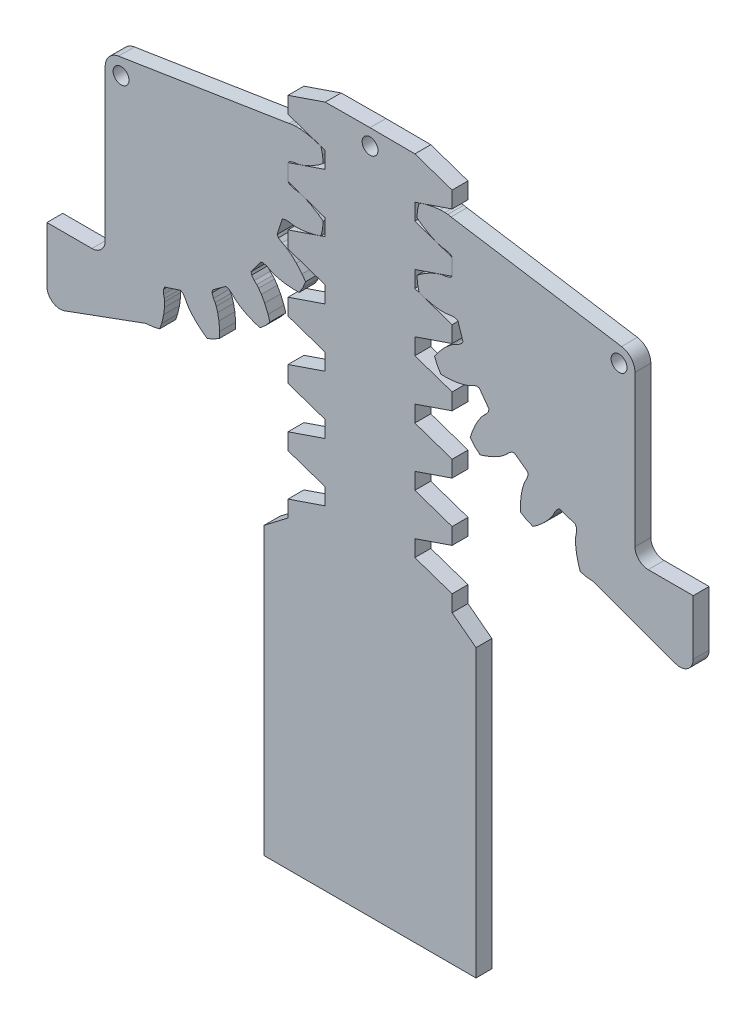
SolidWorks part; units mm, degrees
note: The reader was unsure of these and kept them because the rebuilt part matched: shared geometry of "Model<4>", "Model<5>".
other "verr_centre"
other "verr_droit"
other "verr_gauche"
ref_plane "Plan de face" through (0, 0, 0) normal (0, 0, 1) x (1, 0, 0)
ref_plane "Plan de dessus" through (0, 0, 0) normal (0, 1, 0) x (1, 0, 0)
ref_plane "Plan de droite" through (0, 0, 0) normal (1, 0, 0) x (0, 0, -1)
sketch "Model" plane through (0, 0, 0) normal (0, 0, 1) x (1, 0, 0)
  line L0 (-24, 288) -> (-24, 209.8426) construction
  line L1 (22.0859, 288) -> (22.0859, 218.9084) construction
  line L2 (0, 318) -> (0, 60) construction
  line L288 (24.6849, 293.2827) -> (26.4138, 292.6914)
  line L289 (26.4138, 292.6914) -> (27.4861, 292.4462)
  line L290 (27.4861, 292.4462) -> (28.7039, 292.2992)
  line L291 (28.7039, 292.2992) -> (30.2775, 291.8078)
  line L292 (30.2775, 291.8078) -> (31.0246, 291.1144)
  line L293 (31.0246, 291.1144) -> (31.0246, 284.8856)
  line L294 (31.0246, 284.8856) -> (30.2775, 284.1922)
  line L295 (30.2775, 284.1922) -> (28.7039, 283.7008)
  line L296 (28.7039, 283.7008) -> (27.4861, 283.5538)
  line L297 (27.4861, 283.5538) -> (26.4138, 283.3086)
  line L298 (26.4138, 283.3086) -> (24.6849, 282.7173)
  line L299 (24.6849, 282.7173) -> (22.3675, 281.6425)
  line L300 (22.3675, 281.6425) -> (19.5509, 279.958)
  line L301 (19.5509, 279.958) -> (17.7106, 278.5772)
  line L302 (17.7106, 278.5772) -> (17.9174, 275.9497)
  line L303 (17.9174, 275.9497) -> (18.5327, 273.3869)
  line L304 (18.5327, 273.3869) -> (20.7096, 272.6424)
  line L305 (20.7096, 272.6424) -> (23.9088, 271.9107)
  line L306 (23.9088, 271.9107) -> (26.445, 271.6046)
  line L307 (26.445, 271.6046) -> (28.272, 271.5765)
  line L308 (28.272, 271.5765) -> (29.3676, 271.6746)
  line L309 (29.3676, 271.6746) -> (30.5712, 271.9112)
  line L310 (30.5712, 271.9112) -> (32.2197, 271.9301)
  line L311 (32.2197, 271.9301) -> (33.1445, 271.5015)
  line L312 (33.1445, 271.5015) -> (35.0693, 265.5776)
  line L313 (35.0693, 265.5776) -> (34.573, 264.6873)
  line L314 (34.573, 264.6873) -> (33.2283, 263.7336)
  line L315 (33.2283, 263.7336) -> (32.1155, 263.2175)
  line L316 (32.1155, 263.2175) -> (31.1714, 262.6529)
  line L317 (31.1714, 262.6529) -> (29.7099, 261.5563)
  line L318 (29.7099, 261.5563) -> (27.838, 259.818)
  line L319 (27.838, 259.818) -> (25.6798, 257.3456)
  line L320 (25.6798, 257.3456) -> (24.3563, 255.4636)
  line L321 (24.3563, 255.4636) -> (25.3649, 253.0287)
  line L322 (25.3649, 253.0287) -> (26.742, 250.7814)
  line L323 (26.742, 250.7814) -> (29.0425, 250.746)
  line L324 (29.0425, 250.746) -> (32.3112, 251.0388)
  line L325 (32.3112, 251.0388) -> (34.8178, 251.5314)
  line L326 (34.8178, 251.5314) -> (36.5641, 252.0693)
  line L327 (36.5641, 252.0693) -> (37.5757, 252.5011)
  line L328 (37.5757, 252.5011) -> (38.6474, 253.098)
  line L329 (38.6474, 253.098) -> (40.2093, 253.6254)
  line L330 (40.2093, 253.6254) -> (41.2213, 253.5036)
  line L331 (41.2213, 253.5036) -> (44.8825, 248.4644)
  line L332 (44.8825, 248.4644) -> (44.6856, 247.4643)
  line L333 (44.6856, 247.4643) -> (43.7014, 246.1418)
  line L334 (43.7014, 246.1418) -> (42.8025, 245.3071)
  line L335 (42.8025, 245.3071) -> (42.0792, 244.4784)
  line L336 (42.0792, 244.4784) -> (41.028, 242.9838)
  line L337 (41.028, 242.9838) -> (39.7849, 240.7521)
  line L338 (39.7849, 240.7521) -> (38.4964, 237.7338)
  line L339 (38.4964, 237.7338) -> (37.8192, 235.535)
  line L340 (37.8192, 235.535) -> (39.5309, 233.5309)
  line L341 (39.5309, 233.5309) -> (41.535, 231.8192)
  line L342 (41.535, 231.8192) -> (43.7338, 232.4964)
  line L343 (43.7338, 232.4964) -> (46.7521, 233.7849)
  line L344 (46.7521, 233.7849) -> (48.9838, 235.028)
  line L345 (48.9838, 235.028) -> (50.4784, 236.0792)
  line L346 (50.4784, 236.0792) -> (51.3071, 236.8025)
  line L347 (51.3071, 236.8025) -> (52.1418, 237.7014)
  line L348 (52.1418, 237.7014) -> (53.4643, 238.6856)
  line L349 (53.4643, 238.6856) -> (54.4644, 238.8825)
  line L350 (54.4644, 238.8825) -> (59.5036, 235.2213)
  line L351 (59.5036, 235.2213) -> (59.6254, 234.2093)
  line L352 (59.6254, 234.2093) -> (59.098, 232.6474)
  line L353 (59.098, 232.6474) -> (58.5011, 231.5757)
  line L354 (58.5011, 231.5757) -> (58.0693, 230.5641)
  line L355 (58.0693, 230.5641) -> (57.5314, 228.8178)
  line L356 (57.5314, 228.8178) -> (57.0388, 226.3112)
  line L357 (57.0388, 226.3112) -> (56.746, 223.0425)
  line L358 (56.746, 223.0425) -> (56.7814, 220.742)
  line L359 (56.7814, 220.742) -> (59.0287, 219.3649)
  line L360 (59.0287, 219.3649) -> (61.4636, 218.3563)
  line L361 (61.4636, 218.3563) -> (63.3456, 219.6798)
  line L362 (63.3456, 219.6798) -> (65.818, 221.838)
  line L363 (65.818, 221.838) -> (67.5563, 223.7099)
  line L364 (67.5563, 223.7099) -> (68.6529, 225.1714)
  line L365 (68.6529, 225.1714) -> (69.2175, 226.1155)
  line L366 (69.2175, 226.1155) -> (69.7336, 227.2283)
  line L367 (69.7336, 227.2283) -> (70.6873, 228.573)
  line L368 (70.6873, 228.573) -> (71.5776, 229.0693)
  line L369 (71.5776, 229.0693) -> (77.5015, 227.1445)
  line L370 (77.5015, 227.1445) -> (77.9301, 226.2197)
  line L371 (77.9301, 226.2197) -> (77.9112, 224.5712)
  line L372 (77.9112, 224.5712) -> (77.6746, 223.3676)
  line L373 (77.6746, 223.3676) -> (77.5765, 222.272)
  line L374 (77.5765, 222.272) -> (77.6046, 220.445)
  line L375 (77.6046, 220.445) -> (77.9107, 217.9088)
  line L376 (77.9107, 217.9088) -> (78.6424, 214.7096)
  line L377 (78.6424, 214.7096) -> (79.3869, 212.5327)
  line L378 (79.3869, 212.5327) -> (81.9497, 211.9174)
  line L379 (81.9497, 211.9174) -> (84.5772, 211.7106)
  line L380 (84.5772, 211.7106) -> (115.2804, 200.4655)
  line L381 (122, 205.1605) -> (122, 226)
  line L382 (122, 226) -> (105, 226)
  line L383 (100, 231) -> (100, 288)
  line L384 (94.9357, 293.9266) -> (30.5712, 304.0888)
  line L385 (30.5712, 304.0888) -> (29.3676, 304.3254)
  line L386 (29.3676, 304.3254) -> (28.272, 304.4235)
  line L387 (28.272, 304.4235) -> (26.445, 304.3954)
  line L388 (26.445, 304.3954) -> (23.9088, 304.0893)
  line L389 (23.9088, 304.0893) -> (20.7096, 303.3576)
  line L390 (20.7096, 303.3576) -> (18.5327, 302.6131)
  line L391 (18.5327, 302.6131) -> (17.9174, 300.0503)
  line L392 (17.9174, 300.0503) -> (17.7106, 297.4228)
  line L393 (17.7106, 297.4228) -> (19.5509, 296.042)
  line L394 (19.5509, 296.042) -> (22.3675, 294.3575)
  line L395 (22.3675, 294.3575) -> (24.6849, 293.2827)
  line L396 (-24.6849, 293.2827) -> (-26.4138, 292.6914)
  line L397 (-26.4138, 292.6914) -> (-27.4861, 292.4462)
  line L398 (-27.4861, 292.4462) -> (-28.7039, 292.2992)
  line L399 (-28.7039, 292.2992) -> (-30.2775, 291.8078)
  line L400 (-30.2775, 291.8078) -> (-31.0246, 291.1144)
  line L401 (-31.0246, 291.1144) -> (-31.0246, 284.8856)
  line L402 (-31.0246, 284.8856) -> (-30.2775, 284.1922)
  line L403 (-30.2775, 284.1922) -> (-28.7039, 283.7008)
  line L404 (-28.7039, 283.7008) -> (-27.4861, 283.5538)
  line L405 (-27.4861, 283.5538) -> (-26.4138, 283.3086)
  line L406 (-26.4138, 283.3086) -> (-24.6849, 282.7173)
  line L407 (-24.6849, 282.7173) -> (-22.3675, 281.6425)
  line L408 (-22.3675, 281.6425) -> (-19.5509, 279.958)
  line L409 (-19.5509, 279.958) -> (-17.7106, 278.5772)
  line L410 (-17.7106, 278.5772) -> (-17.9174, 275.9497)
  line L411 (-17.9174, 275.9497) -> (-18.5327, 273.3869)
  line L412 (-18.5327, 273.3869) -> (-20.7096, 272.6424)
  line L413 (-20.7096, 272.6424) -> (-23.9088, 271.9107)
  line L414 (-23.9088, 271.9107) -> (-26.445, 271.6046)
  line L415 (-26.445, 271.6046) -> (-28.272, 271.5765)
  line L416 (-28.272, 271.5765) -> (-29.3676, 271.6746)
  line L417 (-29.3676, 271.6746) -> (-30.5712, 271.9112)
  line L418 (-30.5712, 271.9112) -> (-32.2197, 271.9301)
  line L419 (-32.2197, 271.9301) -> (-33.1445, 271.5015)
  line L420 (-33.1445, 271.5015) -> (-35.0693, 265.5776)
  line L421 (-35.0693, 265.5776) -> (-34.573, 264.6873)
  line L422 (-34.573, 264.6873) -> (-33.2283, 263.7336)
  line L423 (-33.2283, 263.7336) -> (-32.1155, 263.2175)
  line L424 (-32.1155, 263.2175) -> (-31.1714, 262.6529)
  line L425 (-31.1714, 262.6529) -> (-29.7099, 261.5563)
  line L426 (-29.7099, 261.5563) -> (-27.838, 259.818)
  line L427 (-27.838, 259.818) -> (-25.6798, 257.3456)
  line L428 (-25.6798, 257.3456) -> (-24.3563, 255.4636)
  line L429 (-24.3563, 255.4636) -> (-25.3649, 253.0287)
  line L430 (-25.3649, 253.0287) -> (-26.742, 250.7814)
  line L431 (-26.742, 250.7814) -> (-29.0425, 250.746)
  line L432 (-29.0425, 250.746) -> (-32.3112, 251.0388)
  line L433 (-32.3112, 251.0388) -> (-34.8178, 251.5314)
  line L434 (-34.8178, 251.5314) -> (-36.5641, 252.0693)
  line L435 (-36.5641, 252.0693) -> (-37.5757, 252.5011)
  line L436 (-37.5757, 252.5011) -> (-38.6474, 253.098)
  line L437 (-38.6474, 253.098) -> (-40.2093, 253.6254)
  line L438 (-40.2093, 253.6254) -> (-41.2213, 253.5036)
  line L439 (-41.2213, 253.5036) -> (-44.8825, 248.4644)
  line L440 (-44.8825, 248.4644) -> (-44.6856, 247.4643)
  line L441 (-44.6856, 247.4643) -> (-43.7014, 246.1418)
  line L442 (-43.7014, 246.1418) -> (-42.8025, 245.3071)
  line L443 (-42.8025, 245.3071) -> (-42.0792, 244.4784)
  line L444 (-42.0792, 244.4784) -> (-41.028, 242.9838)
  line L445 (-41.028, 242.9838) -> (-39.7849, 240.7521)
  line L446 (-39.7849, 240.7521) -> (-38.4964, 237.7338)
  line L447 (-38.4964, 237.7338) -> (-37.8192, 235.535)
  line L448 (-37.8192, 235.535) -> (-39.5309, 233.5309)
  line L449 (-39.5309, 233.5309) -> (-41.535, 231.8192)
  line L450 (-41.535, 231.8192) -> (-43.7338, 232.4964)
  line L451 (-43.7338, 232.4964) -> (-46.7521, 233.7849)
  line L452 (-46.7521, 233.7849) -> (-48.9838, 235.028)
  line L453 (-48.9838, 235.028) -> (-50.4784, 236.0792)
  line L454 (-50.4784, 236.0792) -> (-51.3071, 236.8025)
  line L455 (-51.3071, 236.8025) -> (-52.1418, 237.7014)
  line L456 (-52.1418, 237.7014) -> (-53.4643, 238.6856)
  line L457 (-53.4643, 238.6856) -> (-54.4644, 238.8825)
  line L458 (-54.4644, 238.8825) -> (-59.5036, 235.2213)
  line L459 (-59.5036, 235.2213) -> (-59.6254, 234.2093)
  line L460 (-59.6254, 234.2093) -> (-59.098, 232.6474)
  line L461 (-59.098, 232.6474) -> (-58.5011, 231.5757)
  line L462 (-58.5011, 231.5757) -> (-58.0693, 230.5641)
  line L463 (-58.0693, 230.5641) -> (-57.5314, 228.8178)
  line L464 (-57.5314, 228.8178) -> (-57.0388, 226.3112)
  line L465 (-57.0388, 226.3112) -> (-56.746, 223.0425)
  line L466 (-56.746, 223.0425) -> (-56.7814, 220.742)
  line L467 (-56.7814, 220.742) -> (-59.0287, 219.3649)
  line L468 (-59.0287, 219.3649) -> (-61.4636, 218.3563)
  line L469 (-61.4636, 218.3563) -> (-63.3456, 219.6798)
  line L470 (-63.3456, 219.6798) -> (-65.818, 221.838)
  line L471 (-65.818, 221.838) -> (-67.5563, 223.7099)
  line L472 (-67.5563, 223.7099) -> (-68.6529, 225.1714)
  line L473 (-68.6529, 225.1714) -> (-69.2175, 226.1155)
  line L474 (-69.2175, 226.1155) -> (-69.7336, 227.2283)
  line L475 (-69.7336, 227.2283) -> (-70.6873, 228.573)
  line L476 (-70.6873, 228.573) -> (-71.5776, 229.0693)
  line L477 (-71.5776, 229.0693) -> (-77.5015, 227.1445)
  line L478 (-77.5015, 227.1445) -> (-77.9301, 226.2197)
  line L479 (-77.9301, 226.2197) -> (-77.9112, 224.5712)
  line L480 (-77.9112, 224.5712) -> (-77.6746, 223.3676)
  line L481 (-77.6746, 223.3676) -> (-77.5765, 222.272)
  line L482 (-77.5765, 222.272) -> (-77.6046, 220.445)
  line L483 (-77.6046, 220.445) -> (-77.9107, 217.9088)
  line L484 (-77.9107, 217.9088) -> (-78.6424, 214.7096)
  line L485 (-78.6424, 214.7096) -> (-79.3869, 212.5327)
  line L486 (-79.3869, 212.5327) -> (-81.9497, 211.9174)
  line L487 (-81.9497, 211.9174) -> (-84.5772, 211.7106)
  line L488 (-84.5772, 211.7106) -> (-115.2804, 200.4655)
  line L489 (-122, 205.1605) -> (-122, 226)
  line L490 (-122, 226) -> (-105, 226)
  line L491 (-100, 231) -> (-100, 288)
  line L492 (-94.9357, 293.9266) -> (-30.5712, 304.0888)
  line L493 (-30.5712, 304.0888) -> (-29.3676, 304.3254)
  line L494 (-29.3676, 304.3254) -> (-28.272, 304.4235)
  line L495 (-28.272, 304.4235) -> (-26.445, 304.3954)
  line L496 (-26.445, 304.3954) -> (-23.9088, 304.0893)
  line L497 (-23.9088, 304.0893) -> (-20.7096, 303.3576)
  line L498 (-20.7096, 303.3576) -> (-18.5327, 302.6131)
  line L499 (-18.5327, 302.6131) -> (-17.9174, 300.0503)
  line L500 (-17.9174, 300.0503) -> (-17.7106, 297.4228)
  line L501 (-17.7106, 297.4228) -> (-19.5509, 296.042)
  line L502 (-19.5509, 296.042) -> (-22.3675, 294.3575)
  line L503 (-22.3675, 294.3575) -> (-24.6849, 293.2827)
  line L504 (-40, 60) -> (0, 60)
  line L505 (0, 60) -> (40, 60)
  line L506 (40, 60) -> (40, 168)
  line L507 (40, 168) -> (30.9746, 174.9084)
  line L508 (30.9746, 174.9084) -> (30.9746, 181.0916)
  line L509 (30.9746, 181.0916) -> (16.919, 185.8989)
  line L510 (16.919, 185.8989) -> (16.919, 192.1011)
  line L511 (16.919, 192.1011) -> (30.9746, 196.9084)
  line L512 (30.9746, 196.9084) -> (30.9746, 203.0916)
  line L513 (30.9746, 203.0916) -> (16.919, 207.8989)
  line L514 (16.919, 207.8989) -> (16.919, 214.1011)
  line L515 (16.919, 214.1011) -> (30.9746, 218.9084)
  line L516 (30.9746, 218.9084) -> (30.9746, 225.0916)
  line L517 (30.9746, 225.0916) -> (16.919, 229.8989)
  line L518 (16.919, 229.8989) -> (16.919, 236.1011)
  line L519 (16.919, 236.1011) -> (30.9746, 240.9084)
  line L520 (30.9746, 240.9084) -> (30.9746, 247.0916)
  line L521 (30.9746, 247.0916) -> (16.919, 251.8989)
  line L522 (16.919, 251.8989) -> (16.919, 258.1011)
  line L523 (16.919, 258.1011) -> (30.9746, 262.9084)
  line L524 (30.9746, 262.9084) -> (30.9746, 269.0916)
  line L525 (30.9746, 269.0916) -> (16.919, 273.8989)
  line L526 (16.919, 273.8989) -> (16.919, 280.1011)
  line L527 (16.919, 280.1011) -> (30.9746, 284.9084)
  line L528 (30.9746, 284.9084) -> (30.9746, 291.0916)
  line L529 (30.9746, 291.0916) -> (16.919, 295.8989)
  line L530 (16.919, 295.8989) -> (16.919, 302.1011)
  line L531 (16.919, 302.1011) -> (30.9746, 306.9084)
  line L532 (30.9746, 306.9084) -> (30.9746, 313.0916)
  line L533 (30.9746, 313.0916) -> (16.919, 317.8989)
  line L534 (16.919, 317.8989) -> (0, 318)
  line L535 (0, 318) -> (-16.919, 317.8989)
  line L536 (-16.919, 317.8989) -> (-30.9746, 313.0916)
  line L537 (-30.9746, 313.0916) -> (-30.9746, 306.9084)
  line L538 (-30.9746, 306.9084) -> (-16.919, 302.1011)
  line L539 (-16.919, 302.1011) -> (-16.919, 295.8989)
  line L540 (-16.919, 295.8989) -> (-30.9746, 291.0916)
  line L541 (-30.9746, 291.0916) -> (-30.9746, 284.9084)
  line L542 (-30.9746, 284.9084) -> (-16.919, 280.1011)
  line L543 (-16.919, 280.1011) -> (-16.919, 273.8989)
  line L544 (-16.919, 273.8989) -> (-30.9746, 269.0916)
  line L545 (-30.9746, 269.0916) -> (-30.9746, 262.9084)
  line L546 (-30.9746, 262.9084) -> (-16.919, 258.1011)
  line L547 (-16.919, 258.1011) -> (-16.919, 251.8989)
  line L548 (-16.919, 251.8989) -> (-30.9746, 247.0916)
  line L549 (-30.9746, 247.0916) -> (-30.9746, 240.9084)
  line L550 (-30.9746, 240.9084) -> (-16.919, 236.1011)
  line L551 (-16.919, 236.1011) -> (-16.919, 229.8989)
  line L552 (-16.919, 229.8989) -> (-30.9746, 225.0916)
  line L553 (-30.9746, 225.0916) -> (-30.9746, 218.9084)
  line L554 (-30.9746, 218.9084) -> (-16.919, 214.1011)
  line L555 (-16.919, 214.1011) -> (-16.919, 207.8989)
  line L556 (-16.919, 207.8989) -> (-30.9746, 203.0916)
  line L557 (-30.9746, 203.0916) -> (-30.9746, 196.9084)
  line L558 (-30.9746, 196.9084) -> (-16.919, 192.1011)
  line L559 (-16.919, 192.1011) -> (-16.919, 185.8989)
  line L560 (-16.919, 185.8989) -> (-30.9746, 181.0916)
  line L561 (-30.9746, 181.0916) -> (-30.9746, 174.9084)
  line L562 (-30.9746, 174.9084) -> (-40, 168)
  line L563 (-40, 168) -> (-40, 60)
  circle A0 centre (94, 288) radius 3
  circle A1 centre (0, 312) radius 3
  circle A5 centre (-94, 288) radius 70 construction
  circle A6 centre (94, 288) radius 71.9141 construction
  arc A8 (115.2804, 200.4655) -> (122, 205.1605) centre (117, 205.1605) ccw
  arc A9 (100, 231) -> (105, 226) centre (105, 231) ccw
  arc A10 (100, 288) -> (94.9357, 293.9266) centre (94, 288) ccw
  arc A11 (-122, 205.1605) -> (-115.2804, 200.4655) centre (-117, 205.1605) ccw
  arc A12 (-105, 226) -> (-100, 231) centre (-105, 231) ccw
  arc A13 (-94.9357, 293.9266) -> (-100, 288) centre (-94, 288) ccw
  circle A14 centre (-94, 288) radius 3
extrude "Boss.-Extru.1" add sketch "Model" along normal blind 6 contours A1 | L536 L537 L538 L539 L540 L541 L542 L543 L544 L545 L546 L547 L548 L549 L550 L551 L552 L553 L554 L555 L556 L557 L558 L559 L560 L561 L562 L563 L504 L505 L506 L507 L508 L509 L510 L511 L512 L513 L514 L515 L516 L517 L518 L519 L520 L521 L522 L523 L524 L525 L526 L527 L528 L529 L530 L531 L532 L533 L534 L535
extrude "Boss.-Extru.2" add sketch "Model<4>" along normal blind 6 separate body contours L492 A13 L491 A12 L490 L489 A11 L488 L487 L486 L485 L484 L483 L482 L481 L480 L479 L478 L477 L476 L475 L474 L473 L472 L471 L470 L469 L468 L467 L466 L465 L464 L463 L462 L461 L460 L459 L458 L457 L456 L455 L454 L453 L452 L451 L450 L449 L448 L447 L446 L445
sketch "Model<4>" plane through (0, 0, 0) normal (0, 0, 1) x (1, 0, 0) same geometry as "Model"
extrude "Boss.-Extru.3" add sketch "Model<5>" along normal blind 6 separate body contours L383 A10 L384 L385 L386 L387 L388 L389 L390 L391 L392 L393 L394 L395 L288 L289 L290 L291 L292 L293 L294 L295 L296 L297 L298 L299 L300 L301 L302 L303 L304 L305 L306 L307 L308 L309 L310 L311 L312 L313 L314 L315 L316 L317 L318 L319 L320 L321 L322 L323 L324
sketch "Model<5>" plane through (0, 0, 0) normal (0, 0, 1) x (1, 0, 0) same geometry as "Model"
other "Enregistrer les corps1"
